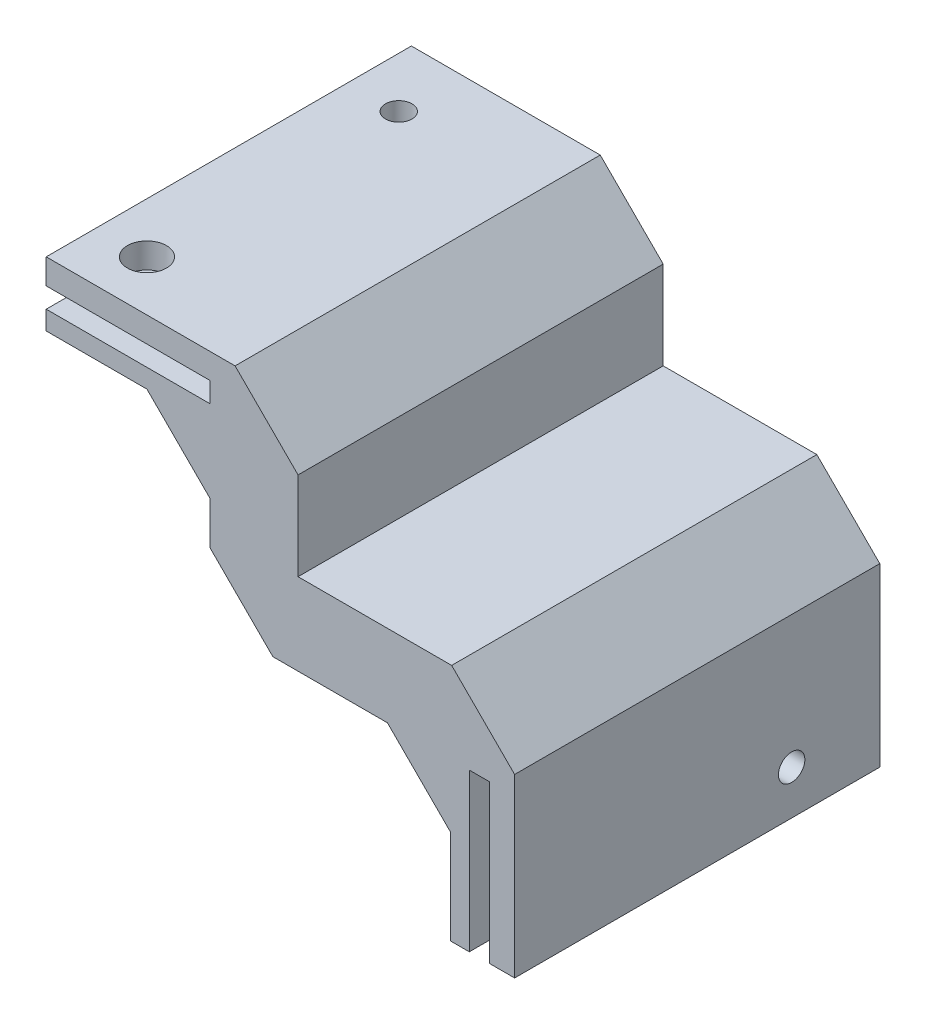
SolidWorks part; units mm, degrees
material "ABS"
ref_plane "Płaszczyzna przednia" through (0, 0, 0) normal (0, 0, 1) x (1, 0, 0)
ref_plane "Płaszczyzna górna" through (0, 0, 0) normal (0, 1, 0) x (1, 0, 0)
ref_plane "Płaszczyzna prawa" through (0, 0, 0) normal (1, 0, 0) x (0, 0, -1)
sketch "Szkic1" plane through (0, 0, 0) normal (0, 0, 1) x (1, 0, 0)
  line L0 (0, 0) -> (-4, 0)
  line L1 (-4, 0) -> (-4, 15)
  line L2 (-4, 15) -> (-7.2, 15)
  line L3 (-7.2, 15) -> (-7.2, 0)
  line L4 (-7.2, 0) -> (-10.2, 0)
  line L5 (-10.2, 0) -> (-10.2, 15)
  line L6 (0, 0) -> (0, 28)
  line L7 (0, 28) -> (-34.4, 28)
  line L8 (-10.2, 15) -> (-38.4, 15)
  line L9 (-34.4, 28) -> (-34.4, 52)
  line L10 (-34.4, 52) -> (-74.4, 52)
  line L11 (-74.4, 52) -> (-74.4, 48)
  line L12 (-74.4, 48) -> (-48.4, 48)
  line L13 (-48.4, 48) -> (-48.4, 44.8)
  line L14 (-48.4, 44.8) -> (-74.4, 44.8)
  line L15 (-74.4, 44.8) -> (-74.4, 41.8)
  line L16 (-74.4, 41.8) -> (-48.4, 41.8)
  line L17 (-48.4, 41.8) -> (-48.4, 25)
  line L18 (-48.4, 25) -> (-38.4, 15)
  dimension "D1" = 4
  dimension "D2" = 3
  dimension "D3" = 3.2
  dimension "D4" = 15
  dimension "D5" = 28
  dimension "D6" = 34.4
  dimension "D7" = 28.2
  dimension "D8" = 4
  dimension "D9" = 3.2
  dimension "D10" = 3
  dimension "D11" = 26
  dimension "D12" = 14
  dimension "D13" = 24
  dimension "D14" = 16.8
extrude "Dodanie-wyciągnięcie1" add sketch "Szkic1" along normal blind 58
chamfer "Sfazowanie1" distance 10 angle 45 4 edges at (-10.2, 15, 29) (-48.4, 41.8, 29) (0, 28, 29) (-34.4, 52, 29)
sketch "Szkic2" plane through (0, 0, 0) normal (0, -1, 0) x (1, 0, 0)
  line L0 (-4, 0) -> (0, 0) construction
  line L1 (0, 0) -> (0, 58) construction
  line L2 (0, 58) -> (-4, 58) construction
  line L3 (-4, 58) -> (-4, 0) construction
  line L4 (-10.2, 0) -> (-7.2, 0) construction
  line L5 (-7.2, 0) -> (-7.2, 58) construction
  line L6 (-7.2, 58) -> (-10.2, 58) construction
  line L7 (-10.2, 58) -> (-10.2, 0) construction
  line L8 (-4, 0) -> (0, 0)
  line L9 (0, 0) -> (0, 58)
  line L10 (0, 58) -> (-4, 58)
  line L11 (-4, 58) -> (-4, 0)
  line L12 (-10.2, 0) -> (-7.2, 0)
  line L13 (-7.2, 0) -> (-7.2, 58)
  line L14 (-7.2, 58) -> (-10.2, 58)
  line L15 (-10.2, 58) -> (-10.2, 0)
extrude "Dodanie-wyciągnięcie2" add sketch "Szkic2" along normal blind 10
sketch "Szkic3" plane through (0, 41.8, 0) normal (0, -1, 0) x (1, 0, 0)
  line L0 (-74.4, 58) -> (-58.4, 58) construction
  line L1 (-74.4, 0) -> (-58.4, 0) construction
  line L2 (-74.4, 58) -> (-74.4, 0) construction
  circle A0 centre (-66.4, 10) radius 2.1
  circle A1 centre (-66.4, 50) radius 3.1
  point P8 (0, 0)
  dimension "D1" = 8
  dimension "D4" = 6.2
  dimension "D5" = 4.2
  dimension "D2" = 10
  dimension "D3" = 8
extrude "Wytnij-wyciągnięcie1" cut sketch "Szkic3" against normal through all contours A0 | A1
sketch "Szkic4" plane through (-10.2, 0, 0) normal (-1, 0, 0) x (0, 0, 1)
  line L0 (58, 5) -> (0, 5) construction
  line L1 (0, 5) -> (0, -10) construction
  circle A0 centre (14, -3) radius 2.1
  dimension "D1" = 4.2
  dimension "D2" = 8
  dimension "D3" = 14
extrude "Wytnij-wyciągnięcie2" cut sketch "Szkic4" against normal through all
